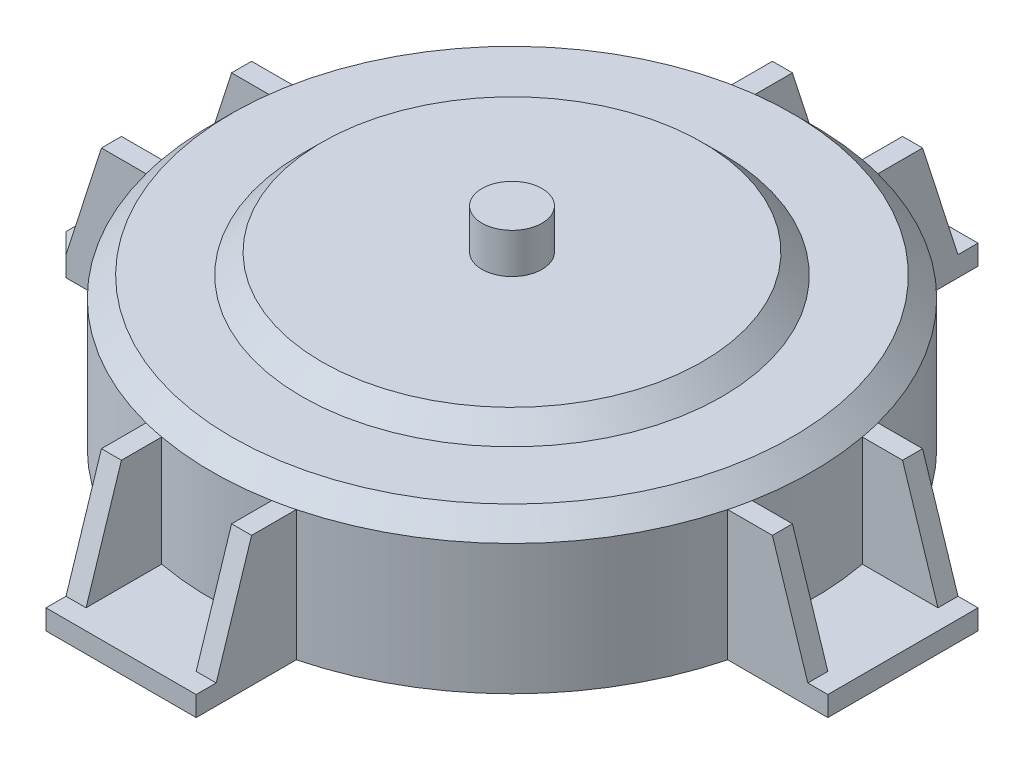
SolidWorks part; units mm, degrees
ref_plane "Front Plane" through (0, 0, 0) normal (0, 0, 1) x (1, 0, 0)
ref_plane "Top Plane" through (0, 0, 0) normal (0, 1, 0) x (1, 0, 0)
ref_plane "Right Plane" through (0, 0, 0) normal (1, 0, 0) x (0, 0, -1)
sketch "Sketch1" plane through (0, 0, 0) normal (0, 1, 0) x (1, 0, 0)
  circle A0 centre (0, 0) radius 150
extrude "Boss-Extrude1" add sketch "Sketch1" along normal blind 75
chamfer "Chamfer1" distance 10 angle 45 1 edges at (0, 75, 150)
sketch "Sketch4" plane through (0, 0, 0) normal (0, -1, 0) x (1, 0, 0)
  line L1 (-195.2369, 37.5) -> (-145.2369, 37.5)
  line L2 (-195.2369, 37.5) -> (-195.2369, -37.5)
  line L3 (-195.2369, -37.5) -> (-145.2369, -37.5)
  circle A0 centre (0, 0) radius 150 construction
  circle A1 centre (0, 0) radius 150
  point P0 (-150, 0)
  circle M5 centre (0, 0) radius 150
  dimension "D1" = 50
  dimension "D2" = 75
extrude "Boss-Extrude2" add sketch "Sketch4" against normal blind 10 contours L2 L3 L1 M5 region at (-171.8083, 0, 0)
chamfer "Chamfer2" distance 10 angle 45 2 edges at (-195.2369, 5, 37.5) (-195.2369, 5, -37.5)
sketch "Sketch5" plane through (0, 0, 37.5) normal (0, 0, 1) x (1, 0, 0)
  line L0 (-145.2369, 10) -> (-145.2369, 65)
  line L1 (-150, 65) -> (150, 65) construction
  line L2 (-145.2369, 65) -> (-167.5569, 65)
  line L3 (-167.5569, 65) -> (-185.2369, 10)
  line L4 (-185.2369, 10) -> (-145.2369, 10)
  line L5 (-185.2369, 10) -> (-185.2369, 0) construction
  line L6 (-185.2369, 10) -> (-145.2369, 10) construction
  dimension "D1" = 17.68
extrude "Boss-Extrude3" add sketch "Sketch5" against normal blind 10
mirror "Mirror1" about plane through (0, 0, 0) normal (0, 0, 1) of "Boss-Extrude3"
pattern_circular "CirPattern1" count 4 over 360 about axis through (0, 0, 0) along (0, 1, 0) of "Boss-Extrude3", "Boss-Extrude2", "Mirror1"
sketch "Sketch8" plane through (0, 75, 0) normal (0, 1, 0) x (1, 0, 0)
  circle A0 centre (0, 0) radius 110
extrude "Boss-Extrude5" add sketch "Sketch8" along normal blind 10
chamfer "Chamfer3" distance 15 angle 45 1 edges at (0, 85, 110)
sketch "Sketch9" plane through (0, 85, 0) normal (0, 1, 0) x (1, 0, 0)
  circle A0 centre (0, 0) radius 15
extrude "Boss-Extrude6" add sketch "Sketch9" along normal blind 20
scale "Scale1" scale about centroid uniform scaling yes scale factor 0.45
sketch "Sketch10" plane through (0, 21.3447, 0) normal (0, -1, 0) x (-1, 0, 0)
  text T0 "<b>IITG</b>" font "Century Gothic" height in points 72
extrude "Cut-Extrude1" cut sketch "Sketch10" against normal blind 2
